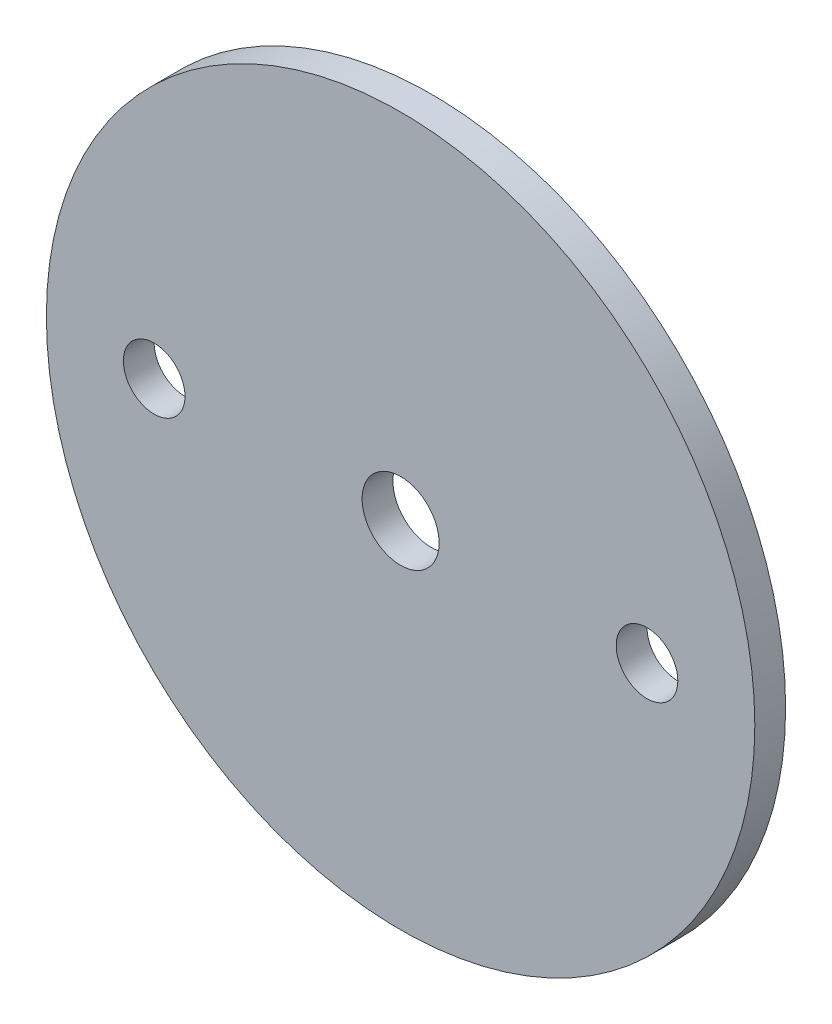
SolidWorks part; units mm, degrees
ref_plane "Front Plane" through (0, 0, 0) normal (0, 0, 1) x (1, 0, 0)
ref_plane "Top Plane" through (0, 0, 0) normal (0, 1, 0) x (1, 0, 0)
ref_plane "Right Plane" through (0, 0, 0) normal (1, 0, 0) x (0, 0, -1)
sketch "Sketch1" plane through (0, 0, 0) normal (0, 0, 1) x (1, 0, 0)
  circle A0 centre (0, 0) radius 36.5125
  dimension "D1" = 73.025
extrude "Boss-Extrude1" add sketch "Sketch1" along normal mid plane 3.175
sketch "Sketch2" plane through (0, 0, 1.5875) normal (0, 0, 1) x (1, 0, 0)
  line L0 (-1000, 0) -> (49000, 0) construction
  line L1 (0, -1000) -> (0, 49000) construction
  point P4 (25.4, 0)
  point P5 (-25.4, 0)
  dimension "D2" = 50.8
  dimension "D1" = 25.4
hole_wizard "1/4 (0.25) Diameter Hole1" positions "Sketch2" profile "Sketch3" hole size "1/4" standard "ANSI Inch" end condition through all
sketch "Sketch3" plane through (-25.4, 0, 1.5875) normal (1, 0, 0) x (0, -1, 0)
  line L0 (0, 0) -> (0, 3.175)
  line L1 (0, 3.175) -> (3.175, 3.175)
  line L2 (3.175, 3.175) -> (3.175, 0)
  line L5 (3.175, 0) -> (0, 0)
  line L11 (0, -6.35) -> (0, 107.95) construction
  dimension "Thru Hole Dia." = 6.35
  dimension "Thru Hole Depth" = 3.175
sketch "Sketch4" plane through (0, 0, 1.5875) normal (0, 0, 1) x (1, 0, 0)
  point P0 (0, 0)
hole_wizard "5/16 (0.3125) Diameter Hole1" positions "Sketch4" profile "Sketch5" hole size "5/16" standard "ANSI Inch"
sketch "Sketch5" plane through (0, 0, 1.5875) normal (1, 0, 0) x (0, -1, 0)
  line L0 (0, 0) -> (0, 3.302)
  line L1 (0, 3.302) -> (3.9687, 3.302)
  line L2 (3.9687, 3.302) -> (3.9688, 0)
  line L5 (3.9688, 0) -> (0, 0)
  line L10 (0, 3.302) -> (-3.9688, 3.302) construction
  line L11 (0, -6.35) -> (0, 107.95) construction
  dimension "Hole Dia." = 7.9375
  dimension "Hole Depth" = 3.302
  dimension "Drill Angle" = 180
equation "\"AIRFRAME_OD\"= 3.091in"
equation "\"AIRFRAME_ID\"= 3.00in"
equation "\"FLAT_T\"= 0.125in"
equation "\"NOSE_EXP_L\"= 3.5in"
equation "\"NOSE_SHOULDER_L\"= 5in"
equation "\"MAIN_L\"= 30in"
equation "\"RECO_COUP_L\"= 6in"
equation "\"RECO_SWITCH_L\"= 1.5in"
equation "\"DROGUE_L\"= 14in"
equation "\"ATS_FORE_COUP_L\"= 4in"
equation "\"ATS_AFT_COUP_L\"= 2.5in"
equation "\"LOWER_L\"= 16in"
equation "\"FIN_N\"= 4"
equation "\"CR_AFT_X\"= 0.5in"
equation "\"CR_FORE_X\"= 6in"
equation "\"FIN_ROOT\"= 5in"
equation "\"FIN_X\"= 0.75in"
equation "\"MOTOR_OD\"= 2.25in"
equation "\"MOTOR_ID\"= 2.126in"
equation "\"COUPLER_OD\"= 2.998in"
equation "\"COUPLER_ID\"= 2.875in"
equation "\"D1@Sketch1\"=\"COUPLER_ID\""
equation "\"D1@Boss-Extrude1\"=\"FLAT_T\""
equation "\"RECO_ROD_X\"= 1.5in"
equation "\"ATS_ROD_X\"= 2in"
equation "\"D2@Sketch2\"=\"ATS_ROD_X\""
